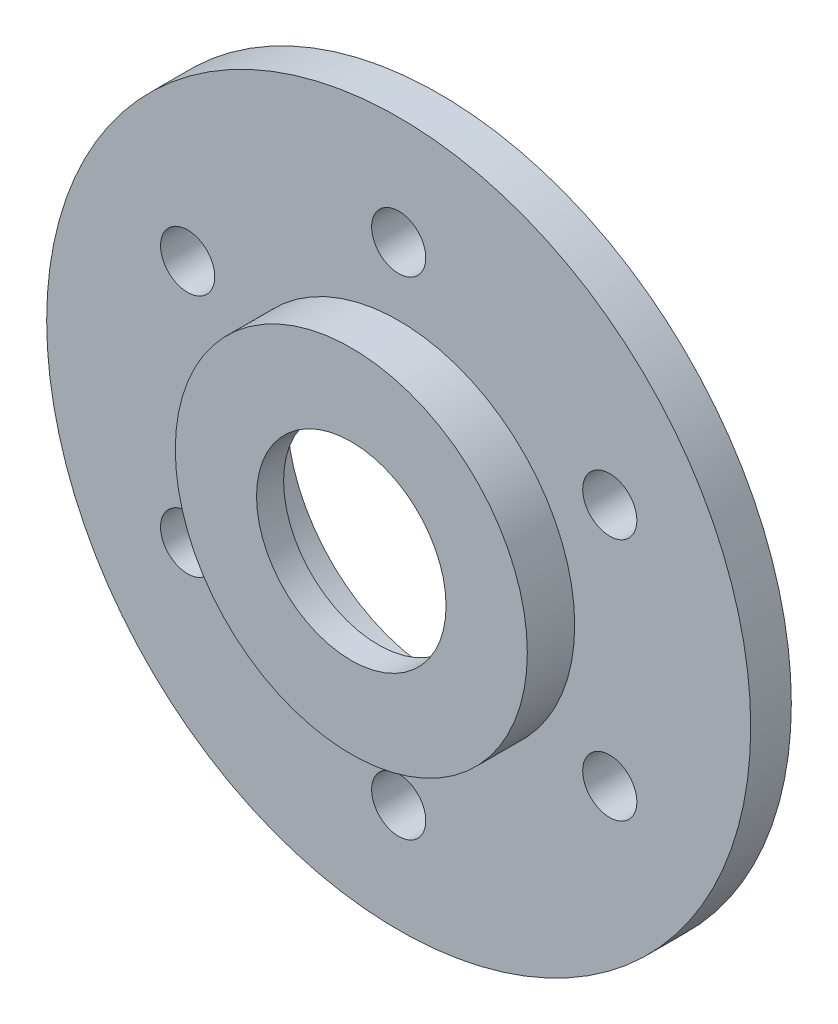
SolidWorks part; units mm, degrees
material "Resina de melamina"
ref_plane "Alzado" through (0, 0, 0) normal (0, 0, 1) x (1, 0, 0)
ref_plane "Planta" through (0, 0, 0) normal (0, 1, 0) x (1, 0, 0)
ref_plane "Vista lateral" through (0, 0, 0) normal (1, 0, 0) x (0, 0, -1)
sketch "Croquis1" plane through (0, 0, 0) normal (0, 0, 1) x (1, 0, 0)
  circle A0 centre (0, 0) radius 7
  circle A1 centre (0, 0) radius 13
  dimension "D1" = 14
  dimension "D2" = 26
extrude "Saliente-Extruir1" add sketch "Croquis1" along normal blind 4
sketch "Croquis2" plane through (0, 0, 0) normal (0, 0, -1) x (-1, 0, 0)
  circle A1 centre (0, 0) radius 26
  circle A2 centre (0, 0) radius 11.25
  dimension "D1" = 52
  dimension "D2" = 22.5
extrude "Saliente-Extruir2" add sketch "Croquis2" against normal mid plane 3 separate body
sketch "Croquis3" plane through (0, 0, -1.5) normal (0, 0, -1) x (-1, 0, 0)
  line L0 (0, 0) -> (0, 18) construction
  line L1 (0, 18) -> (0, 26) construction
  line L2 (0, 18) -> (0, 18.876) construction
  circle A0 centre (0, 18) radius 2
  circle A1 centre (0, 0) radius 26 construction
  circle A2 centre (15.5885, 9) radius 2
  circle A3 centre (15.5885, -9) radius 2
  circle A4 centre (0, -18) radius 2
  circle A5 centre (-15.5885, -9) radius 2
  circle A6 centre (-15.5885, 9) radius 2
  dimension "D3" = 4
  dimension "D1" = 18
  dimension "D2" = 6
extrude "Cortar-Extruir1" cut sketch "Croquis3" against normal through all
sketch "Croquis4" plane through (0, 0, -1.5) normal (0, 0, -1) x (-1, 0, 0)
  circle A0 centre (0, 0) radius 11.25
extrude "Cortar-Extruir2" cut sketch "Croquis4" against normal blind 4.5
sketch "Croquis5" plane through (0, 0, 4) normal (0, 0, 1) x (1, 0, 0)
  circle A0 centre (0, 0) radius 13
  circle A1 centre (0, 0) radius 7
extrude "Saliente-Extruir3" add sketch "Croquis5" along normal blind 1
